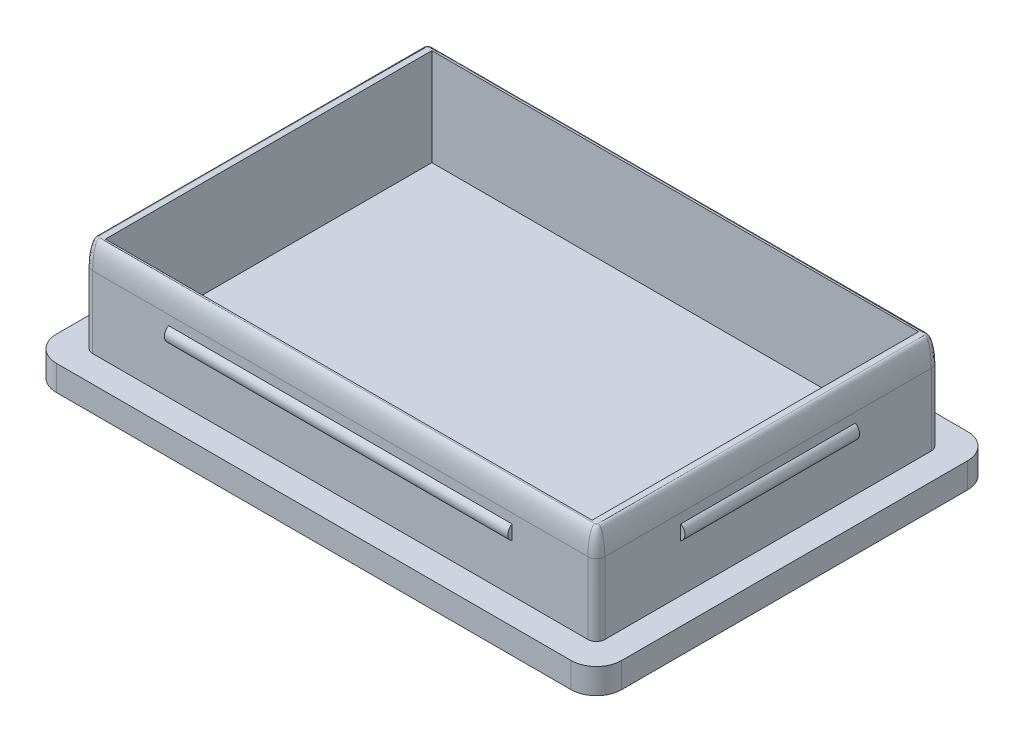
SolidWorks part; units mm, degrees
ref_plane "Front Plane" through (0, 0, 0) normal (0, 0, 1) x (1, 0, 0)
ref_plane "Top Plane" through (0, 0, 0) normal (0, 1, 0) x (1, 0, 0)
ref_plane "Right Plane" through (0, 0, 0) normal (1, 0, 0) x (0, 0, -1)
sketch "Sketch1" plane through (0, 0, 0) normal (0, 1, 0) x (1, 0, 0)
  line L1 (-30.5, 20.5) -> (30.5, 20.5)
  line L2 (-30.5, 20.5) -> (-30.5, -20.5)
  line L3 (-30.5, -20.5) -> (30.5, -20.5)
  line L4 (30.5, 20.5) -> (30.5, -20.5)
  line L5 (-30.5, 20.5) -> (30.5, -20.5) construction
  line L6 (-30.5, -20.5) -> (30.5, 20.5) construction
  point P0 (0, 0)
  dimension "D1" = 61
  dimension "D2" = 41
extrude "Boss-Extrude1" add sketch "Sketch1" along normal blind 23
shell "Shell1" thickness 3 removed face at (0, 23, 0) outward yes
sketch "Sketch2" plane through (0, 23, 0) normal (0, 1, 0) x (1, 0, 0)
  line L1 (-33.5, 23.5) -> (33.5, 23.5)
  line L2 (-33.5, 23.5) -> (-33.5, -23.5)
  line L3 (-33.5, -23.5) -> (33.5, -23.5)
  line L4 (33.5, 23.5) -> (33.5, -23.5)
extrude "Cut-Extrude1" cut sketch "Sketch2" against normal up to surface (23 mm away) up to face at (0, 0, 0)
sketch "Sketch3" plane through (0, 0, 0) normal (0, 1, 0) x (1, 0, 0)
  line L1 (-30.35, 20.35) -> (30.35, 20.35)
  line L2 (-30.35, 20.35) -> (-30.35, -20.35)
  line L3 (-30.35, -20.35) -> (30.35, -20.35)
  line L4 (30.5, 20.5) -> (-30.5, 20.5)
  line L5 (30.5, -20.5) -> (30.5, 20.5)
  line L6 (-30.5, -20.5) -> (30.5, -20.5)
  line L7 (-30.5, 20.5) -> (-30.5, -20.5)
  line L8 (30.5, 20.5) -> (-30.5, 20.5) construction
  line L9 (30.5, -20.5) -> (30.5, 20.5) construction
  line L10 (-30.5, -20.5) -> (30.5, -20.5) construction
  line L11 (-30.5, 20.5) -> (-30.5, -20.5) construction
  line L12 (30.35, 20.35) -> (30.35, -20.35)
  line L13 (-30.35, 20.35) -> (30.35, -20.35) construction
  line L14 (-30.35, -20.35) -> (30.35, 20.35) construction
  line L15 (-28.85, 19.35) -> (28.85, 19.35)
  line L16 (-28.85, 19.35) -> (-28.85, -19.35)
  line L17 (-28.85, -19.35) -> (28.85, -19.35)
  line L18 (28.85, 19.35) -> (28.85, -19.35)
  line L19 (-28.85, 19.35) -> (28.85, -19.35) construction
  line L20 (-28.85, -19.35) -> (28.85, 19.35) construction
  point P0 (0, 0)
  point P10 (0, 0)
  dimension "D2" = 0.15
  dimension "D3" = 0.15
  dimension "D4" = 1
  dimension "D5" = 1.5
  dimension "D1" = 0
extrude "Boss-Extrude2" add sketch "Sketch3" along normal blind 11.5
sketch "Sketch4" plane through (0, 0, 20.35) normal (0, 0, 1) x (1, 0, 0)
  line L0 (-30.35, 11.5) -> (30.35, 11.5) construction
  line L1 (-30.35, 11.5) -> (-30.35, 0) construction
  line L2 (0, 0) -> (0, 16.7449) construction
  circle A0 centre (-29.85, 6.5) radius 1
  circle A1 centre (29.85, 6.5) radius 1
  dimension "D2" = 2
  dimension "D3" = 0.5
  dimension "D1" = 5
extrude "Boss-Extrude3" add sketch "Sketch4" against normal offset from surface (20.7 mm away) 10 from offset 10 up to face at (0, 5.75, -20.35) offset against normal yes
sketch "Sketch5" plane through (30.35, 0, 0) normal (1, 0, 0) x (0, 0, -1)
  line L0 (-20.35, 11.5) -> (20.35, 11.5) construction
  line L1 (-20.35, 11.5) -> (-20.35, 0) construction
  line L2 (0, 0) -> (0, 14.2856) construction
  circle A0 centre (-19.85, 6.5) radius 1
  circle A1 centre (19.85, 6.5) radius 1
  line M4 (20.35, 0) -> (20.35, 11.5)
  line M6 (-20.35, 11.5) -> (-20.35, 0)
  dimension "D1" = 2
  dimension "D2" = 5
  dimension "D3" = 0.5
extrude "Boss-Extrude4" add sketch "Sketch5" against normal offset from surface (40.7 mm away) 10 from offset 10 contours A0 M6 | A1 M4 region at (30.35, 6.5, 20.555) region at (30.35, 6.5, -20.555) up to face at (-30.35, 6.5, 0) offset against normal yes
fillet "Fillet1" radius 3 4 edges at (33.5, -1.5, 23.5) (33.5, -1.5, -23.5) (-33.5, -1.5, -23.5) (-33.5, -1.5, 23.5)
fillet "Fillet2" radius 1 4 edges at (-30.35, 5.75, -20.35) (-30.35, 5.75, 20.35) (30.35, 5.75, 20.35) (30.35, 5.75, -20.35)
fillet "Fillet3" radius 3 8 edges at (30.35, 11.5, 0) (30.0571, 11.5, -20.0571) (30.0571, 11.5, 20.0571) (0, 11.5, -20.35) (0, 11.5, 20.35) (-30.0571, 11.5, -20.0571) (-30.0571, 11.5, 20.0571) (-30.35, 11.5, 0) second distance 0.8 first distance on face at (30.35, 5.75, 0) first distance on face at (29.9536, 5.75, -19.9536) first distance on face at (29.9536, 5.75, 19.9536) first distance on face at (0, 6.5, -20.35) first distance on face at (0, 6.5, 20.35) first distance on face at (-29.9536, 5.75, -19.9536) first distance on face at (-29.9536, 5.75, 19.9536) first distance on face at (-30.35, 6.5, 0)
